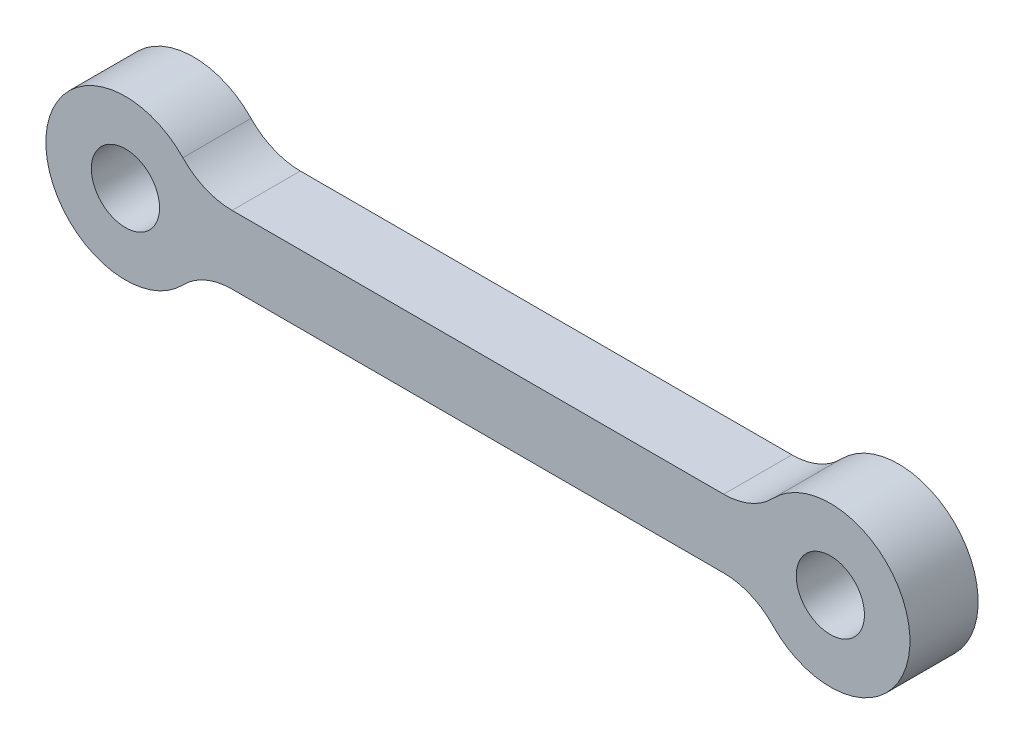
SolidWorks part; units mm, degrees
material "PET"
ref_plane "Front Plane" through (0, 0, 0) normal (0, 0, 1) x (1, 0, 0)
ref_plane "Top Plane" through (0, 0, 0) normal (0, 1, 0) x (1, 0, 0)
ref_plane "Right Plane" through (0, 0, 0) normal (1, 0, 0) x (0, 0, -1)
sketch "Sketch1" plane through (0, 0, 0) normal (0, 0, 1) x (1, 0, 0)
  line L0 (0, 0) -> (31, 0) construction
  line L1 (0, 3.5) -> (31, 3.5) construction
  line L2 (0, -3.5) -> (31, -3.5) construction
  line L3 (15.5, 0) -> (15.5, -3.5) construction
  line L5 (3.1623, 1.5) -> (27.8377, 1.5)
  line L6 (3.1623, 1.5) -> (3.1623, -1.5) construction
  line L7 (3.1623, -1.5) -> (27.8377, -1.5)
  line L8 (27.8377, 1.5) -> (27.8377, -1.5) construction
  line L9 (3.1623, 1.5) -> (27.8377, -1.5) construction
  line L10 (3.1623, -1.5) -> (27.8377, 1.5) construction
  arc A0 (0, 3.5) -> (0, -3.5) centre (0, 0) ccw construction
  arc A1 (31, -3.5) -> (31, 3.5) centre (31, 0) ccw construction
  circle A2 centre (0, 0) radius 1.5
  circle A3 centre (0, 0) radius 3.5
  circle A4 centre (31, 0) radius 1.5
  circle A5 centre (31, 0) radius 3.5
  point P3 (15.5, 0)
  point P20 (15.5, 1.5)
  dimension "D3" = 3
  dimension "D1" = 31
  dimension "D2" = 7
extrude "Boss-Extrude1" add sketch "Sketch1" along normal blind 3 contours A3 A2 | A5 L5 A3 L7 | A5 A4 region at (15.5, 0, 0) region at (3.3179, 0.747, 0) region at (31.747, 3.3179, 0)
fillet "Fillet1" radius 3 4 edges at (27.8377, -1.5, 1.5) (3.1623, -1.5, 1.5) (27.8377, 1.5, 1.5) (3.1623, 1.5, 1.5)
